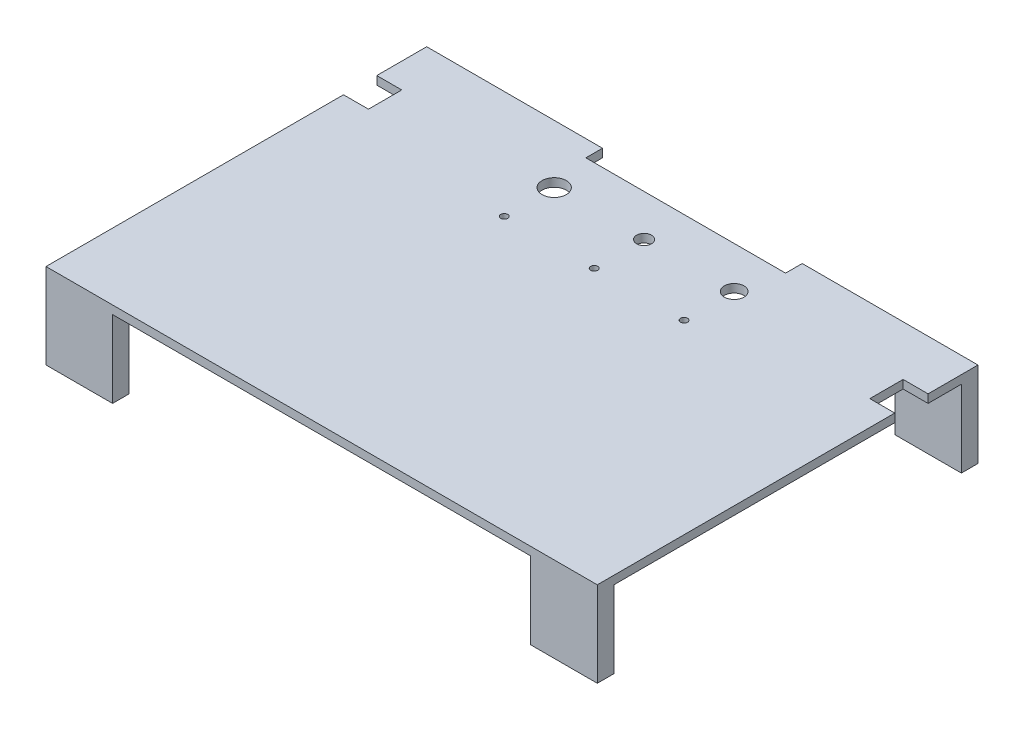
SolidWorks part; units mm, degrees
ref_plane "Front Plane" through (0, 0, 0) normal (0, 0, 1) x (1, 0, 0)
ref_plane "Top Plane" through (0, 0, 0) normal (0, 1, 0) x (1, 0, 0)
ref_plane "Right Plane" through (0, 0, 0) normal (1, 0, 0) x (0, 0, -1)
sketch "Sketch1" plane through (0, 0, 0) normal (0, 1, 0) x (1, 0, 0)
  line L1 (-210.3438, -145.2563) -> (210.3438, -145.2563)
  line L2 (-210.3438, -145.2563) -> (-210.3438, 145.2562)
  line L3 (-210.3438, 145.2562) -> (210.3438, 145.2562)
  line L4 (210.3438, -145.2563) -> (210.3438, 145.2562)
  line L5 (-210.3438, -145.2563) -> (210.3438, 145.2562) construction
  line L6 (-210.3438, 145.2562) -> (210.3438, -145.2563) construction
  point P0 (0, 0)
  dimension "D1" = 420.6875
  dimension "D2" = 290.5125
extrude "Desktop" add sketch "Sketch1" along normal blind 6.35
sketch "Sketch2" plane through (0, 6.35, 0) normal (0, 1, 0) x (1, 0, 0)
  line L0 (210.3438, -145.2563) -> (210.3438, 145.2562) construction
  line L1 (210.3438, 107.1563) -> (191.2937, 107.1562)
  line L2 (210.3438, 107.1563) -> (210.3438, 81.7562)
  line L3 (210.3438, 81.7562) -> (191.2937, 81.7562)
  line L4 (191.2937, 107.1562) -> (191.2937, 81.7562)
  line L5 (210.3438, 145.2562) -> (-210.3438, 145.2562) construction
  line L13 (0, 163.3994) -> (0, -159.0824) construction
  line L14 (-210.3438, 81.7562) -> (-191.2937, 81.7562)
  line L15 (-191.2937, 107.1562) -> (-191.2937, 81.7562)
  line L16 (-210.3438, 107.1563) -> (-191.2937, 107.1562)
  line L17 (-210.3438, 107.1563) -> (-210.3438, 81.7562)
  dimension "D1" = 38.1
  dimension "D2" = 63.5
  dimension "D3" = 19.05
extrude "Brief Case Arm Cutout" cut sketch "Sketch2" against normal blind 6.35 contours L2 L1 L4 L3 | L14 L15 L16 L17
sketch "Sketch5" plane through (0, 6.35, 0) normal (0, 1, 0) x (1, 0, 0)
  line L0 (210.3438, 145.2562) -> (-210.3438, 145.2562) construction
  line L1 (-76.2, 132.5562) -> (76.2, 132.5562)
  line L2 (-76.2, 132.5562) -> (-76.2, 145.2562)
  line L3 (-76.2, 145.2562) -> (76.2, 145.2562)
  line L4 (76.2, 132.5562) -> (76.2, 145.2562)
  line L5 (-76.2, 132.5562) -> (76.2, 145.2562) construction
  line L6 (-76.2, 145.2562) -> (76.2, 132.5562) construction
  point P0 (0, 138.9062)
  point P7 (0, 0)
  dimension "D1" = 152.4
  dimension "D2" = 12.7
extrude "HDMI Screen Cutout" cut sketch "Sketch5" against normal blind 16.51
sketch "Sketch8" plane through (0, 6.35, 0) normal (0, 1, 0) x (1, 0, 0)
  line L0 (210.3438, 107.1563) -> (210.3438, 145.2562) construction
  line L1 (-210.3438, 145.2562) -> (-210.3438, 107.1563) construction
  line L2 (-76.2, 145.2562) -> (-210.3438, 145.2562) construction
  circle A0 centre (68.7387, 100.8062) radius 7.493
  circle A1 centre (-68.6118, 100.8062) radius 9.271
  circle A2 centre (0, 100.8062) radius 5.715
  circle A3 centre (-68.6118, 62.7062) radius 2.667
  circle A6 centre (0, 62.7063) radius 2.667
  circle A7 centre (68.6118, 62.7063) radius 2.667
  dimension "D2" = 14.986
  dimension "D4" = 18.542
  dimension "D6" = 11.43
  dimension "D8" = 5.334
  dimension "D1" = 141.605
  dimension "D3" = 141.732
  dimension "D5" = 44.45
  dimension "D9" = 3
  dimension "D7" = 38.1
extrude "Switches and Lights" cut sketch "Sketch8" against normal blind 16.51
sketch "Sketch10" plane through (0, 0, 0) normal (0, -1, 0) x (1, 0, 0)
  line L0 (-159.5437, 145.2563) -> (-210.3438, 145.2563)
  line L1 (-210.3438, 145.2563) -> (210.3438, 145.2563) construction
  line L2 (-210.3438, 145.2563) -> (-210.3438, 132.5563)
  line L6 (-197.6438, 132.5563) -> (-159.5437, 132.5563)
  line L7 (-159.5437, 132.5563) -> (-159.5437, 145.2563)
  line L8 (159.5438, -132.5562) -> (159.5438, -145.2562)
  line L9 (159.5438, -145.2562) -> (210.3438, -145.2562)
  line L13 (197.6438, -132.5562) -> (159.5438, -132.5562)
  line L15 (-197.6438, 132.5563) -> (-210.3438, 132.5563)
  line L16 (197.6438, -132.5562) -> (210.3438, -132.5562)
  line L17 (210.3438, -107.1563) -> (210.3438, -145.2562) construction
  line L18 (210.3437, -145.2562) -> (210.3438, -107.1562) [skipped]
  line L19 (210.3438, -132.5562) -> (210.3438, -145.2562)
  point P20 (0, 0)
  dimension "D1" = 50.8
  dimension "D3" = 12.7
  dimension "D5" = 2
extrude "Legs" add sketch "Sketch10" along normal blind 58.7375
sketch "Sketch12" plane through (0, 0, 0) normal (0, -1, 0) x (1, 0, 0)
  line L0 (159.5437, 145.2563) -> (210.3438, 145.2563)
  line L1 (-159.5437, 145.2563) -> (210.3438, 145.2563) construction
  line L2 (210.3438, 145.2563) -> (210.3438, 132.5563)
  line L6 (197.6438, 132.5563) -> (159.5437, 132.5563)
  line L7 (159.5437, 132.5563) -> (159.5437, 145.2563)
  line L8 (-159.5437, -132.5563) -> (-159.5437, -145.2563)
  line L9 (-159.5437, -145.2563) -> (-210.3437, -145.2563)
  line L10 (-210.3437, -145.2563) -> (-210.3437, -132.5563)
  line L13 (-197.6437, -132.5563) -> (-159.5437, -132.5563)
  line L14 (197.6438, 132.5563) -> (210.3438, 132.5563)
  line L15 (-197.6437, -132.5563) -> (-210.3437, -132.5563)
  point P20 (0, 0)
  dimension "D1" = 50.8
  dimension "D4" = 12.7
  dimension "D5" = 2
extrude "Legs 2.0" add sketch "Sketch12" along normal blind 58.7375
